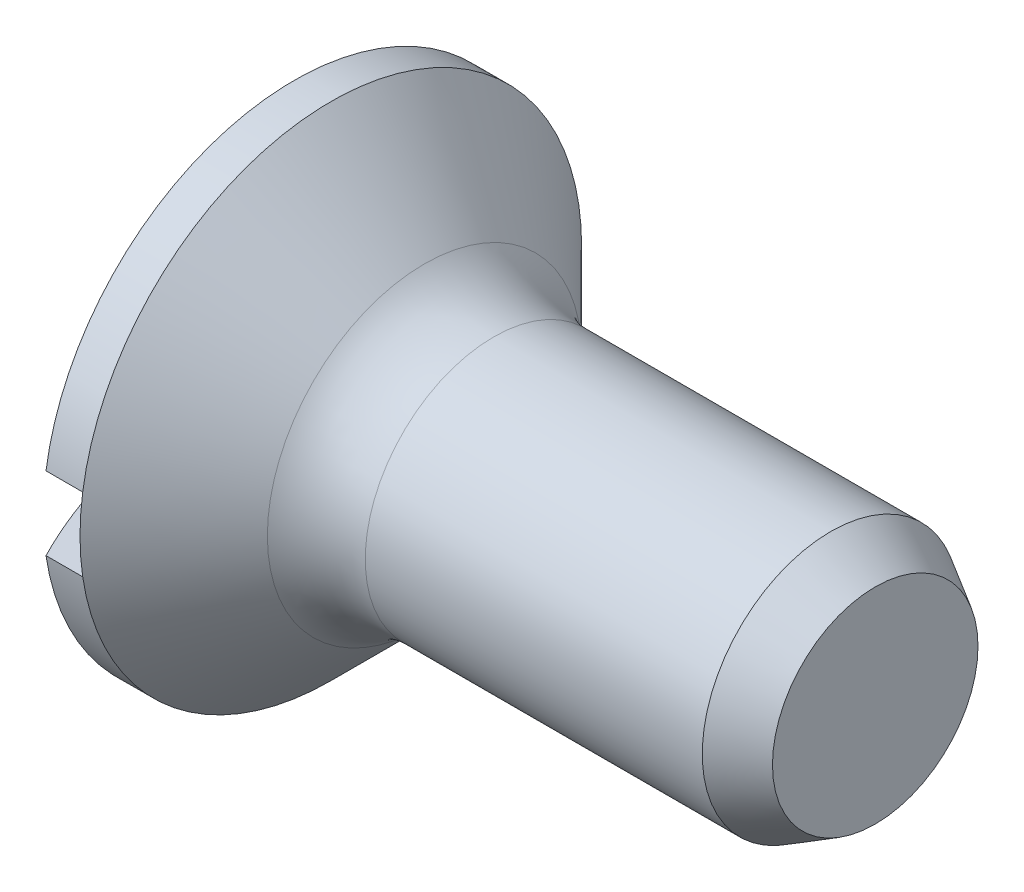
SolidWorks part; units mm, degrees
ref_plane "Front" through (0, 0, 0) normal (0, 0, 1) x (1, 0, 0)
ref_plane "Top" through (0, 0, 0) normal (0, 1, 0) x (1, 0, 0)
ref_plane "Right" through (0, 0, 0) normal (1, 0, 0) x (0, 0, -1)
sketch "Sketch1" plane through (0, 0, 0) normal (0, 0, 1) x (1, 0, 0)
  line L0 (0, 4.1) -> (0.6, 4.1)
  line L1 (0.6, 4.1) -> (2.6, 2.1)
  line L2 (2.6, 2.1) -> (9.5, 2.1)
  line L3 (9.5, 2.1) -> (9.5, 0)
  line L4 (9.5, 0) -> (0, 0)
  line L5 (0, 0) -> (0, 4.1) construction
  line L6 (6.6207, 0) -> (-1, 0) construction
  line L7 (-1, 0) -> (-1, -0.1422) construction
  line L8 (0, 0) -> (-1, 0)
  arc A1 (0, 4.1) -> (-1, 0) centre (7.905, 0) ccw
  dimension "D1" = 45
  dimension "k" = 2.6
revolve "Revolve1" add sketch "Sketch1" angle 360 about L6
cosmetic thread "ThreadCosmetic" [suppressed] parameters "D2"=3.1
sketch "Sketch2" plane through (0, 0, 0) normal (0, 0, 1) x (1, 0, 0)
  line L1 (-1, 0.6) -> (0.6, 0.6)
  line L2 (-1, 0.6) -> (-1, -0.6)
  line L3 (-1, -0.6) -> (0.6, -0.6)
  line L4 (0.6, 0.6) -> (0.6, -0.6)
  line L5 (0, 0) -> (-1, 0) construction
  arc A0 (0, 4.1) -> (-1, 0) centre (7.905, 0) ccw construction
  dimension "n" = 1.2
  dimension "t" = 1.6
extrude "Cut-Extrude1" cut sketch "Sketch2" against normal through all and the other way through all
chamfer "Chamfer1" distance 0.42 angle 60 1 edges at (9.5, 2.1, 0) first distance on face at (9.5, 2.1, 0)
sketch "Sketch4" plane through (0, 0, 0) normal (0, 0, 1) x (1, 0, 0)
  line L0 (3.8225, 1.55) -> (3.0575, 1.55)
  line L1 (3.0575, 1.55) -> (2.74, 2.1)
  line L2 (3.8225, 1.55) -> (4.14, 2.1)
  line L3 (2.74, 2.1) -> (2.74, 2.35)
  line L4 (4.14, 2.1) -> (4.14, 2.35)
  line L5 (2.74, 2.35) -> (4.14, 2.35)
  line L6 (3.44, 1.55) -> (3.44, 0) construction
  line L7 (0, 0) -> (7.3035, 0) construction
  line L9 (2.6, 2.1) -> (2.6, -2.1) construction
  line L12 (8.7725, 2.1) -> (2.6, 2.1) construction
  dimension "D2" = 60
  dimension "D3" = 0.25
  dimension "minordia" = 3.1
  dimension "threadstart" = 0.84
revolve "ThreadSchematic" [suppressed] cut sketch "Sketch4" angle 360 about L7
pattern_linear "ThdSchPat" [suppressed] count 5 spacing 1.4 along (1, 0, 0) of bodies 137
sketch "Sketch3" plane through (0, 0, 0) normal (0, 0, 1) x (1, 0, 0)
  line L0 (2.6, 2.1) -> (9.5, 2.1) construction
  line L2 (5.8, 2.1) -> (6.725, 2.1) construction
  line L3 (9.5, 2.1) -> (9.5, 0) construction
  line L4 (6.725, 2.1) -> (9.5, 0)
  line L5 (2.9, 0) -> (5.4301, 0) construction
  line L6 (9.5, 0) -> (9.7, 0)
  line L7 (9.7, 0) -> (9.7, 2.1)
  line L8 (9.7, 2.1) -> (9.5, 2.1)
  line L9 (6.725, 2.1) -> (9.5, 2.1)
  dimension "D1" = 0.925
revolve "EndCone" [suppressed] cut sketch "Sketch3" angle 360 about L5
fillet "Fillet1" radius 1.6 1 edges at (2.6, 2.1, 0)
equation "\"minordia@Sketch4\" = \"D2@ThreadCosmetic\""
equation "\"D1@Chamfer1\" = \"d@Sketch1\" / 10"
equation "\"D1@Sketch3\" = \"y@Sketch3\" / 4"
equation "\"threadstart@Sketch4\" = \"advance@Sketch4\"*0.6"
equation "\"D1@ThdSchPat\" = int(((\"l@Sketch1\"-\"k@Sketch1\")/\"advance@Sketch4\") + 0.999)"
equation "\"D3@ThdSchPat\" = \"advance@Sketch4\""
